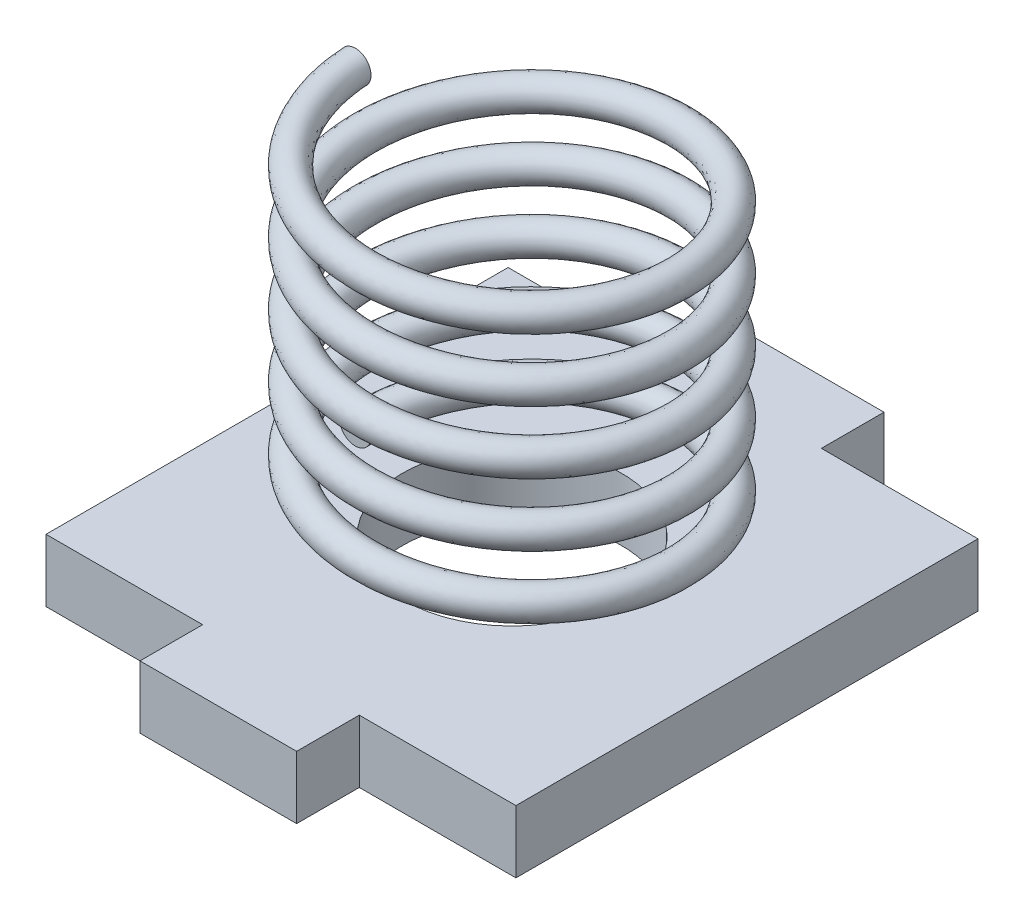
SolidWorks part; units mm, degrees
ref_plane "Front Plane" through (0, 0, 0) normal (0, 0, 1) x (1, 0, 0)
ref_plane "Top Plane" through (0, 0, 0) normal (0, 1, 0) x (1, 0, 0)
ref_plane "Right Plane" through (0, 0, 0) normal (1, 0, 0) x (0, 0, -1)
sketch "Sketch2" plane through (0, 0, 0) normal (0, 1, 0) x (1, 0, 0)
  line L1 (5, 0) -> (10, 0)
  line L2 (0, 2) -> (0, 16.75)
  line L3 (5, 18.75) -> (10, 18.75)
  line L4 (15, 2) -> (15, 16.75)
  line L7 (0, 16.75) -> (5, 16.75)
  line L8 (5, 18.75) -> (5, 16.75)
  line L11 (15, 16.75) -> (10, 16.75)
  line L12 (10, 18.75) -> (10, 16.75)
  line L13 (0, 2) -> (5, 2)
  line L14 (5, 0) -> (5, 2)
  line L15 (15, 2) -> (10, 2)
  line L16 (10, 0) -> (10, 2)
  dimension "D1" = 2
  dimension "D2" = 2
  dimension "D3" = 5
  dimension "D4" = 2
  dimension "D5" = 18.75
extrude "Boss-Extrude1" add sketch "Sketch2" along normal blind 2
sketch "Sketch3" plane through (0, 2, 0) normal (0, 1, 0) x (1, 0, 0)
  line L0 (10, 18.75) -> (5, 18.75) construction
  circle A0 centre (7.5, 9.375) radius 3.5
  dimension "D1" = 7
  dimension "D2" = 9.375
extrude "Cut-Extrude1" cut sketch "Sketch3" against normal blind 12.4 contours A0
ref_plane "Plane2" through (0, 2.5, 0) normal (0, 1, 0) x (1, 0, 0)
sketch "Sketch7" plane through (0, 2.5, 0) normal (0, 1, 0) x (1, 0, 0)
  circle A0 centre (7.5, 9.375) radius 5
curve "Helix/Spiral2" pitch 2 height 10 turns 5
ref_plane "Plane3" through (0, 0, -9.375) normal (0, 0, 1) x (1, 0, 0)
sketch "Sketch8" plane through (0, 0, -9.375) normal (0, 0, 1) x (1, 0, 0)
  circle A0 centre (2.5, 12.5) radius 0.5
  spline S0 degree 3 poles (2.5, 2.5) (2.5, 2.5414) (2.7603, 2.6251) (3.8724, 2.75) (5.5368, 2.875) (7.5, 3) (9.4632, 3.125) (11.1276, 3.25) (12.2397, 3.375) (12.6302, 3.5) (12.2397, 3.625) (11.1276, 3.75) (9.4632, 3.875) (7.5, 4) (5.5368, 4.125) (3.8724, 4.25) (2.7603, 4.375) (2.3698, 4.5) (2.7603, 4.625) (3.8724, 4.75) (5.5368, 4.875) (7.5, 5) (9.4632, 5.125) (11.1276, 5.25) (12.2397, 5.375) (12.6302, 5.5) (12.2397, 5.625) (11.1276, 5.75) (9.4632, 5.875) (7.5, 6) (5.5368, 6.125) (3.8724, 6.25) (2.7603, 6.375) (2.3698, 6.5) (2.7603, 6.625) (3.8724, 6.75) (5.5368, 6.875) (7.5, 7) (9.4632, 7.125) (11.1276, 7.25) (12.2397, 7.375) (12.6302, 7.5) (12.2397, 7.625) (11.1276, 7.75) (9.4632, 7.875) (7.5, 8) (5.5368, 8.125) (3.8724, 8.25) (2.7603, 8.375) (2.3698, 8.5) (2.7603, 8.625) (3.8724, 8.75) (5.5368, 8.875) (7.5, 9) (9.4632, 9.125) (11.1276, 9.25) (12.2397, 9.375) (12.6302, 9.5) (12.2397, 9.625) (11.1276, 9.75) (9.4632, 9.875) (7.5, 10) (5.5368, 10.125) (3.8724, 10.25) (2.7603, 10.375) (2.3698, 10.5) (2.7603, 10.625) (3.8724, 10.75) (5.5368, 10.875) (7.5, 11) (9.4632, 11.125) (11.1276, 11.25) (12.2397, 11.375) (12.6302, 11.5) (12.2397, 11.625) (11.1276, 11.75) (9.4632, 11.875) (7.5, 12) (5.5368, 12.125) (3.8724, 12.25) (2.7603, 12.3749) (2.5, 12.4586) (2.5, 12.5) knots 0 0 0 0 0.0125 0.025 0.0375 0.05 0.0625 0.075 0.0875 0.1 0.1125 0.125 0.1375 0.15 0.1625 0.175 0.1875 0.2 0.2125 0.225 0.2375 0.25 0.2625 0.275 0.2875 0.3 0.3125 0.325 0.3375 0.35 0.3625 0.375 0.3875 0.4 0.4125 0.425 0.4375 0.45 0.4625 0.475 0.4875 0.5 0.5125 0.525 0.5375 0.55 0.5625 0.575 0.5875 0.6 0.6125 0.625 0.6375 0.65 0.6625 0.675 0.6875 0.7 0.7125 0.725 0.7375 0.75 0.7625 0.775 0.7875 0.8 0.8125 0.825 0.8375 0.85 0.8625 0.875 0.8875 0.9 0.9125 0.925 0.9375 0.95 0.9625 0.975 0.9875 1 1 1 1 construction
sweep "Sweep2" add profiles "Sketch8" path "Helix/Spiral2"
